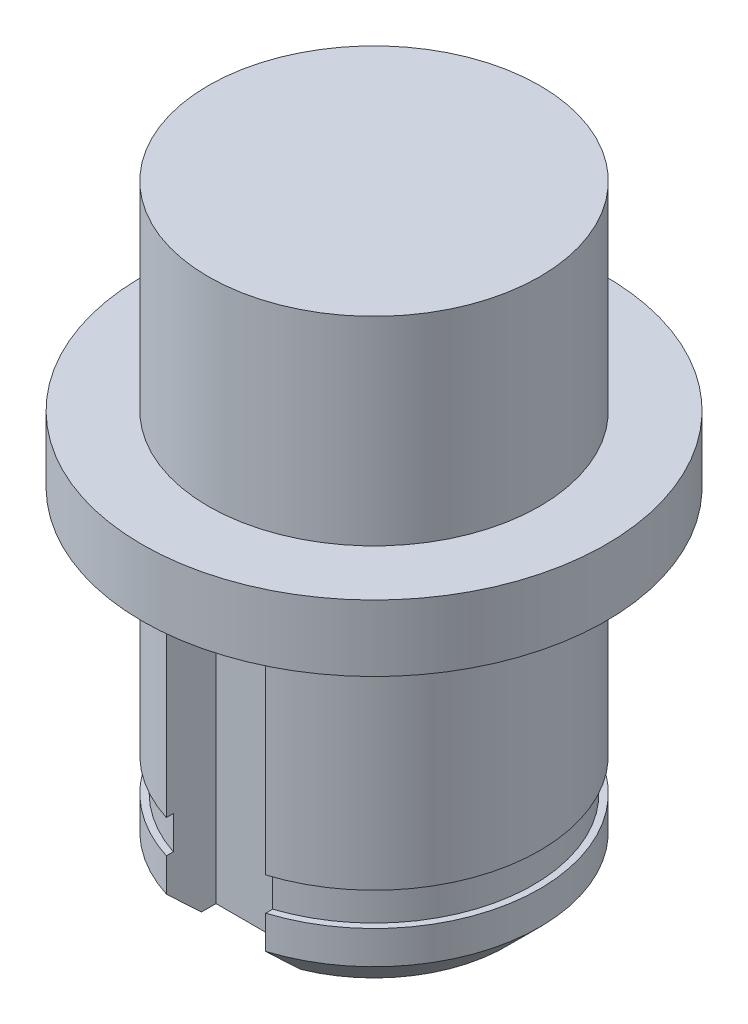
SolidWorks part; units mm, degrees
material "Nylon 101"
ref_plane "Front Plane" through (0, 0, 0) normal (0, 0, 1) x (1, 0, 0)
ref_plane "Top Plane" through (0, 0, 0) normal (0, 1, 0) x (1, 0, 0)
ref_plane "Right Plane" through (0, 0, 0) normal (1, 0, 0) x (0, 0, -1)
sketch "Sketch1" plane through (0, 0, 0) normal (0, 1, 0) x (1, 0, 0)
  circle A0 centre (0, 0) radius 5
  dimension "D1" = 10
extrude "Boss-Extrude1" add sketch "Sketch1" along normal blind 18
ref_axis "Axis1" through (0, 18, 0) along (0, -1, 0)
sketch "Sketch2" plane through (0, 0, 0) normal (1, 0, 0) x (0, 0, -1)
  line L0 (5, 0) -> (5, 18) construction
  line L1 (4.8, 3) -> (5, 3)
  line L2 (4.8, 3) -> (4.8, 2)
  line L3 (4.8, 2) -> (5, 2)
  line L4 (5, 3) -> (5, 2)
  line L5 (5, 18) -> (-5, 18) construction
  line L6 (5, 12) -> (7, 12)
  line L7 (5, 12) -> (5, 10)
  line L8 (5, 10) -> (7, 10)
  line L9 (7, 12) -> (7, 10)
  dimension "D1" = 7
  dimension "D2" = 2
  dimension "D3" = 6
  dimension "D4" = 1
  dimension "D5" = 4.8
  dimension "D6" = 7
revolve "Revolve1" add sketch "Sketch2" angle 360 about axis through (0, 18, 0) along (0, -1, 0) region at (0, 11, -6)
revolve "Cut-Revolve1" cut sketch "Sketch2<5>" angle 360 about axis through (0, 18, 0) along (0, -1, 0) region at (0, 2.5, -4.9)
sketch "Sketch2<5>" plane through (0, 0, 0) normal (1, 0, 0) x (0, 0, -1) same geometry as "Sketch2"
sketch "Sketch4" plane through (0, 0, 0) normal (0, -1, 0) x (1, 0, 0)
  line L0 (0, 0) -> (0, 7.4336) construction
  line L2 (-1.5, 4.7697) -> (-1.5, 3.2697)
  line L3 (-1.5, 3.2697) -> (1.5, 3.2697)
  line L4 (1.5, 4.7697) -> (1.5, 3.2697)
  circle A0 centre (0, 0) radius 5 construction
  dimension "D1" = 1.5
  dimension "D2" = 3
extrude "Cut-Extrude1" cut sketch "Sketch4" against normal blind 10 and the other way through all flip side to cut
chamfer "Chamfer2" distance 1 angle 45 1 edges at (0, 0, -5)
